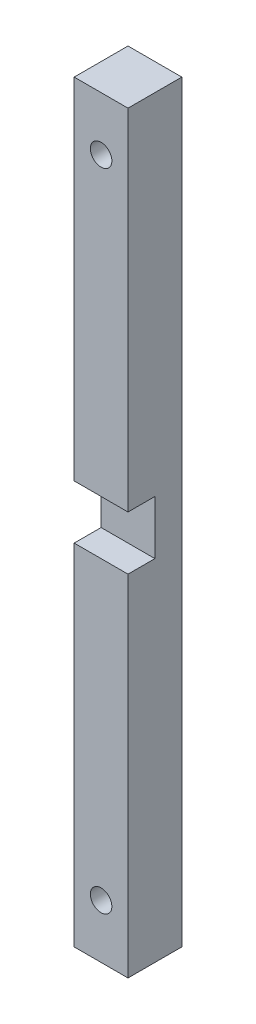
SolidWorks part; units mm, degrees
material "Alloy Steel"
ref_plane "Front Plane" through (0, 0, 0) normal (0, 0, 1) x (1, 0, 0)
ref_plane "Top Plane" through (0, 0, 0) normal (0, 1, 0) x (1, 0, 0)
ref_plane "Right Plane" through (0, 0, 0) normal (1, 0, 0) x (0, 0, -1)
ref_axis "X-Axis" through (-88.99, 0, 0) along (1, 0, 0)
ref_axis "Y-Axis" through (0, 55, 0) along (0, -1, 0)
ref_axis "Z-Axis" through (0, 0, -88.99) along (0, 0, 1)
sketch "Sketch1" plane through (0, 0, 0) normal (0, 0, 1) x (1, 0, 0)
  line L9 (0, 0) -> (10, 0)
  line L10 (0, 0) -> (0, -140)
  line L11 (0, -140) -> (10, -140)
  line L12 (10, 0) -> (10, -140)
  dimension "D1" = 140
  dimension "D2" = 10
extrude "Boss-Extrude1" add sketch "Sketch1" along normal blind 10
sketch "Sketch5" plane through (0, 0, 10) normal (0, 0, 1) x (1, 0, 0)
  line L0 (5, 0) -> (5, -10) construction
  line L1 (10, 0) -> (0, 0) construction
  line L2 (5, -140) -> (5, -130) construction
  line L3 (0, -140) -> (10, -140) construction
  circle A0 centre (5, -10) radius 2
  circle A1 centre (5, -130) radius 2
  dimension "D1" = 4
  dimension "D2" = 120
extrude "Cut-Extrude1" cut sketch "Sketch5" against normal blind 20
sketch "Sketch6" plane through (0, 0, 10) normal (0, 0, 1) x (1, 0, 0)
  line L0 (0, -70) -> (10, -70) construction
  line L1 (0, 0) -> (0, -140) construction
  line L2 (10, -140) -> (10, 0) construction
  line L3 (0, -65) -> (0, -75)
  line L4 (10, -65) -> (10, -75)
  line L5 (0, -65) -> (10, -65)
  line L6 (10, -75) -> (0, -75)
  point P9 (0, -70)
  point P12 (10, -70)
  dimension "D1" = 10
extrude "Cut-Extrude2" cut sketch "Sketch6" against normal blind 5
